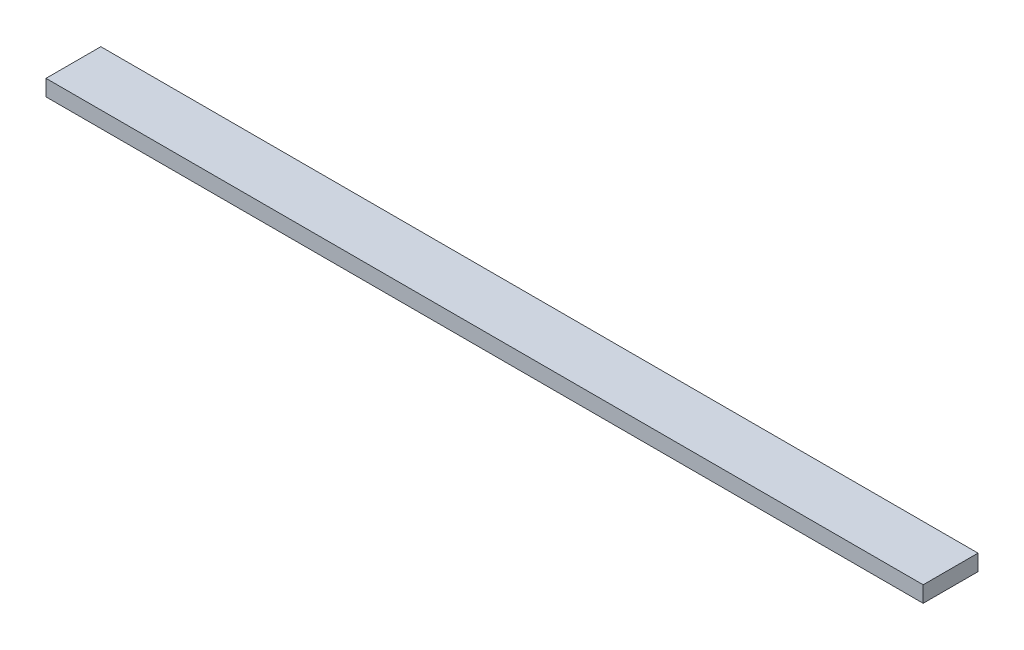
SolidWorks part; units mm, degrees
material "Rubber"
ref_plane "Front" through (0, 0, 0) normal (0, 0, 1) x (1, 0, 0)
ref_plane "Top" through (0, 0, 0) normal (0, 1, 0) x (1, 0, 0)
ref_plane "Right" through (0, 0, 0) normal (1, 0, 0) x (0, 0, -1)
sketch "Sketch1" plane through (0, 0, 0) normal (0, 1, 0) x (1, 0, 0)
  line L1 (-152.4, 9.525) -> (152.4, 9.525)
  line L2 (-152.4, 9.525) -> (-152.4, -9.525)
  line L3 (-152.4, -9.525) -> (152.4, -9.525)
  line L4 (152.4, 9.525) -> (152.4, -9.525)
  line L5 (-152.4, 9.525) -> (152.4, -9.525) construction
  line L6 (-152.4, -9.525) -> (152.4, 9.525) construction
  point P0 (0, 0)
  dimension "D1" = 19.05
  dimension "D2" = 304.8
extrude "Boss-Extrude1" add sketch "Sketch1" along normal blind 5.588
